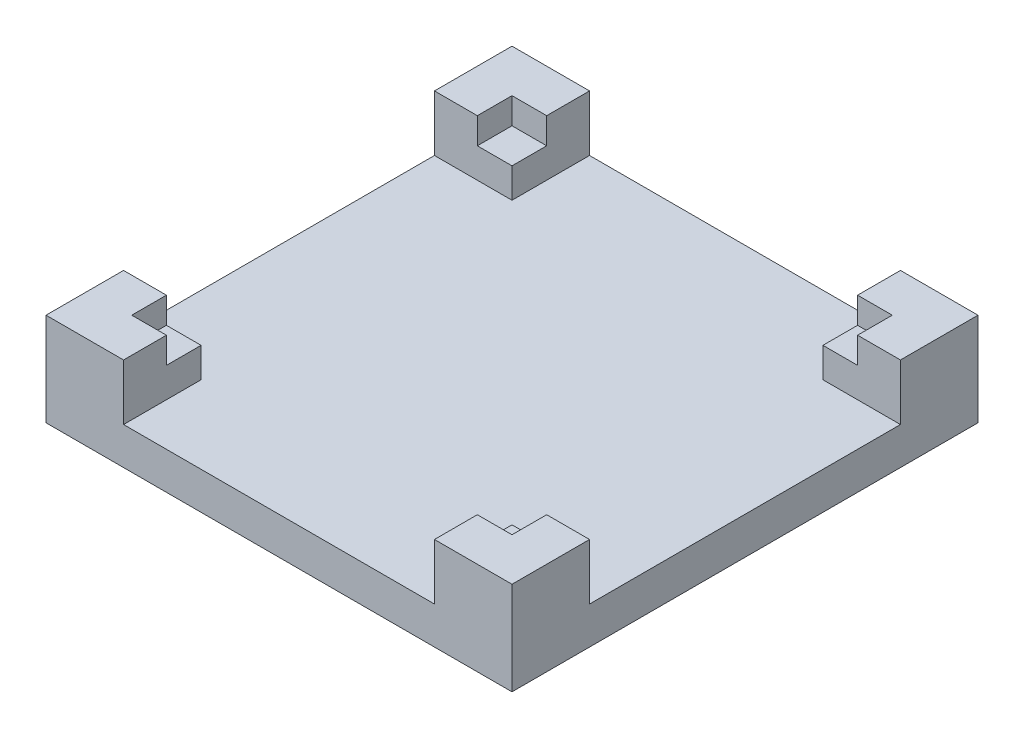
SolidWorks part; units mm, degrees
ref_plane "Front Plane" through (0, 0, 0) normal (0, 0, 1) x (1, 0, 0)
ref_plane "Top Plane" through (0, 0, 0) normal (0, 1, 0) x (1, 0, 0)
ref_plane "Right Plane" through (0, 0, 0) normal (1, 0, 0) x (0, 0, -1)
sketch "Sketch1" plane through (0, 0, 0) normal (0, 1, 0) x (1, 0, 0)
  line L1 (0, 0) -> (125, 0)
  line L2 (0, 0) -> (0, 125)
  line L3 (0, 125) -> (125, 125)
  line L4 (125, 0) -> (125, 125)
  dimension "D1" = 125
  dimension "D2" = 125
extrude "Boss-Extrude1" add sketch "Sketch1" along normal blind 25
sketch "Sketch2" plane through (0, 25, 0) normal (0, 1, 0) x (1, 0, 0)
  line L0 (0, 62.5) -> (125, 62.5) construction
  line L1 (11.5, 11.5) -> (113.5, 11.5)
  line L2 (11.5, 11.5) -> (11.5, 113.5)
  line L3 (11.5, 113.5) -> (113.5, 113.5)
  line L4 (113.5, 11.5) -> (113.5, 113.5)
  line L5 (0, 125) -> (0, 0) construction
  line L6 (62.5, 0) -> (62.5, 125) construction
  line L7 (0, 0) -> (125, 0) construction
  line L8 (125, 0) -> (125, 125) construction
  line L9 (125, 125) -> (0, 125) construction
  point P10 (11.5, 62.5)
  point P17 (62.5, 11.5)
  dimension "D1" = 102
  dimension "D2" = 102
extrude "Cut-Extrude1" cut sketch "Sketch2" against normal blind 15
sketch "Sketch4" plane through (0, 25, 0) normal (0, 1, 0) x (1, 0, 0)
  line L0 (125, 125) -> (0, 125) construction
  line L1 (104.2, 125) -> (20.8, 125)
  line L2 (104.2, 125) -> (104.2, 113.5)
  line L3 (104.2, 113.5) -> (20.8, 113.5)
  line L4 (20.8, 125) -> (20.8, 113.5)
  line L5 (113.5, 113.5) -> (11.5, 113.5) construction
  line L6 (11.5, 113.5) -> (11.5, 11.5) construction
  line L7 (11.5, 104.2) -> (0, 104.2)
  line L8 (11.5, 104.2) -> (11.5, 20.8)
  line L9 (11.5, 20.8) -> (0, 20.8)
  line L10 (0, 104.2) -> (0, 20.8)
  line L11 (0, 125) -> (0, 0) construction
  line L12 (11.5, 11.5) -> (113.5, 11.5) construction
  line L13 (104.2, 11.5) -> (20.8, 11.5)
  line L14 (104.2, 11.5) -> (104.2, 0)
  line L15 (104.2, 0) -> (20.8, 0)
  line L16 (20.8, 11.5) -> (20.8, 0)
  line L17 (0, 0) -> (125, 0) construction
  line L18 (125, 0) -> (125, 125) construction
  line L19 (125, 104.2) -> (113.5, 104.2)
  line L20 (125, 104.2) -> (125, 20.8)
  line L21 (125, 20.8) -> (113.5, 20.8)
  line L22 (113.5, 104.2) -> (113.5, 20.8)
  line L23 (113.5, 11.5) -> (113.5, 113.5) construction
  point P32 (5.75, 20.8)
  dimension "D1" = 9.3
  dimension "D2" = 9.3
  dimension "D3" = 9.3
  dimension "D4" = 9.3
  dimension "D5" = 9.3
  dimension "D6" = 9.3
  dimension "D7" = 9.3
  dimension "D8" = 9.3
extrude "Cut-Extrude2" cut sketch "Sketch4" against normal blind 15
sketch "Sketch5" plane through (0, 10, 0) normal (0, 1, 0) x (1, 0, 0)
  line L1 (113.5, 11.5) -> (104.2, 11.5)
  line L2 (113.5, 11.5) -> (113.5, 20.8)
  line L3 (113.5, 20.8) -> (104.2, 20.8)
  line L4 (104.2, 11.5) -> (104.2, 20.8)
  line L5 (11.5, 11.5) -> (20.8, 11.5)
  line L6 (11.5, 11.5) -> (11.5, 20.8)
  line L7 (11.5, 20.8) -> (20.8, 20.8)
  line L8 (20.8, 11.5) -> (20.8, 20.8)
  line L9 (11.5, 113.5) -> (20.8, 113.5)
  line L10 (11.5, 113.5) -> (11.5, 104.2)
  line L11 (11.5, 104.2) -> (20.8, 104.2)
  line L12 (20.8, 113.5) -> (20.8, 104.2)
  line L13 (113.5, 113.5) -> (104.2, 113.5)
  line L14 (113.5, 113.5) -> (113.5, 104.2)
  line L15 (113.5, 104.2) -> (104.2, 104.2)
  line L16 (104.2, 113.5) -> (104.2, 104.2)
  dimension "D1" = 9.3
  dimension "D2" = 9.3
  dimension "D3" = 9.3
  dimension "D4" = 9.3
  dimension "D5" = 9.3
  dimension "D6" = 9.3
  dimension "D7" = 9.3
  dimension "D8" = 9.3
extrude "Boss-Extrude2" add sketch "Sketch5" along normal blind 8
